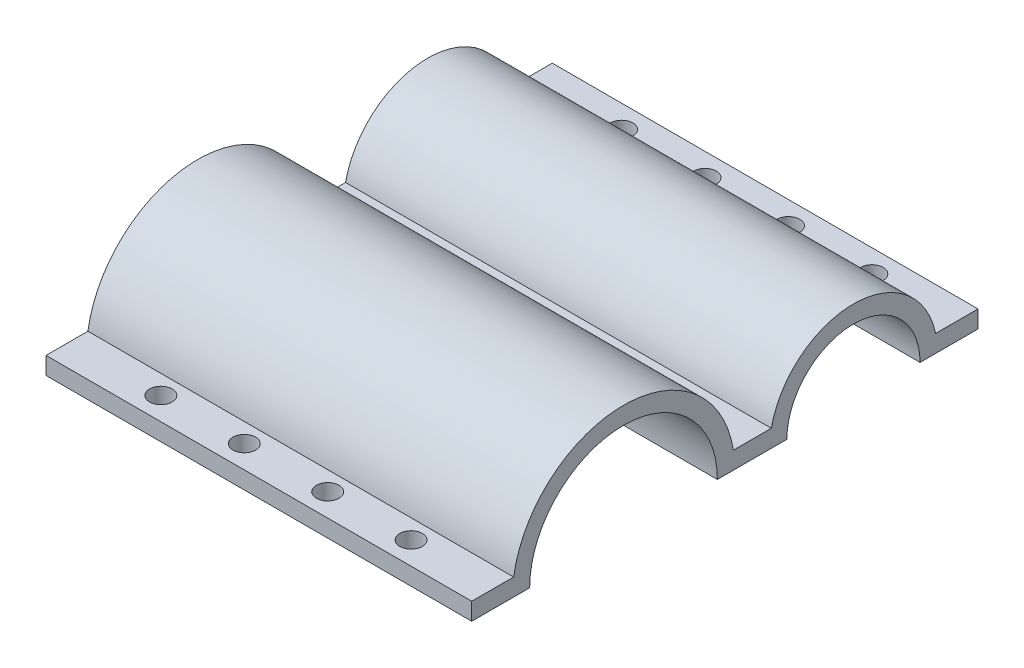
SolidWorks part; units mm, degrees
ref_plane "Front Plane" through (0, 0, 0) normal (0, 0, 1) x (1, 0, 0)
ref_plane "Top Plane" through (0, 0, 0) normal (0, 1, 0) x (1, 0, 0)
ref_plane "Right Plane" through (0, 0, 0) normal (1, 0, 0) x (0, 0, -1)
sketch "Sketch2" plane through (0, 0, 0) normal (1, 0, 0) x (0, 0, -1)
  line L0 (0, 0) -> (-10, 0)
  line L1 (-87.4, 0) -> (-87.4, 3)
  line L3 (0, 3) -> (0, 0)
  line L4 (-33, 0) -> (-45, 0)
  line L5 (-77.4, 0) -> (-87.4, 0)
  line L6 (0, 3) -> (-7.3137, 3)
  line L7 (-35.6863, 3) -> (-42.2358, 3)
  line L8 (-80.1642, 3) -> (-87.4, 3)
  arc A0 (-45, 0) -> (-77.4, 0) centre (-61.2, 0) ccw
  arc A1 (-10, 0) -> (-33, 0) centre (-21.5, 0) ccw
  arc A2 (-7.3137, 3) -> (-35.6863, 3) centre (-21.5, 0) ccw
  arc A3 (-42.2358, 3) -> (-80.1642, 3) centre (-61.2, 0) ccw
  point P9 (-25.1554, 27.7388)
  point P10 (-73.5318, 25.0924)
  point P11 (0, 0)
  point P12 (0, 0)
  dimension "D2" = 16.2
  dimension "D4" = 11.5
  dimension "D3" = 10
  dimension "D1" = 12
  dimension "D6" = 3
extrude "Boss-Extrude1" add sketch "Sketch2" along normal blind 73.5
sketch "Sketch3" plane through (0, 3, 0) normal (0, 1, 0) x (1, 0, 0)
  line L1 (73.5, 0) -> (0, 0) construction
  line L2 (73.5, -3.93) -> (1.5, -3.93) construction
  line L6 (73.5, -87.4) -> (0, -87.4) construction
  line L7 (0, -45) -> (0, -33) construction
  line L8 (0, -39) -> (85.8213, -39) construction
  line L9 (0, -83.47) -> (85.8213, -83.47) construction
  line L10 (0, -45) -> (0, -33) construction
  circle A0 centre (15.9, -3.93) radius 1.95
  circle A1 centre (30.3, -3.93) radius 1.95
  circle A2 centre (44.7, -3.93) radius 1.95
  circle A3 centre (59.1, -3.93) radius 1.95
  circle A4 centre (15.9, -39) radius 1.95
  circle A5 centre (30.3, -39) radius 1.95
  circle A6 centre (44.7, -39) radius 1.95
  circle A7 centre (59.1, -39) radius 1.95
  circle A8 centre (15.9, -83.47) radius 1.95
  circle A9 centre (30.3, -83.47) radius 1.95
  circle A10 centre (44.7, -83.47) radius 1.95
  circle A11 centre (59.1, -83.47) radius 1.95
  point P32 (0, 0)
  point P33 (0, 0)
  point P34 (0, 0)
  point P35 (0, 0)
  point P36 (0, 0)
  point P39 (0, 0)
  point P40 (0, -39)
  point P43 (0, 0)
  point P44 (0, 0)
  point P45 (0, 0)
  point P46 (0, 0)
  point P47 (0, 0)
  point P48 (0, 0)
  point P49 (0, 0)
  point P50 (0, 0)
  point P51 (0, 0)
  point P52 (0, 0)
  point P53 (0, 0)
  point P54 (0.8708, -3.6597)
  dimension "D1" = 3.9
  dimension "D4" = 14.4
  dimension "D5" = 14.4
  dimension "D6" = 14.4
  dimension "D2" = 72
  dimension "D3" = 14.4
  dimension "D7" = 3.93
  dimension "D8" = 3.93
extrude "Cut-Extrude1" cut sketch "Sketch3" against normal up to surface (3 mm away) up to face at (36.75, 0, 82.4)
equation "\"MotorDIA\"= 22'ME 405 Motor Diameter"
equation "\"SyringeDIA\"= 31.4'60ml Syringe Diameter"
equation "\"MotorShaftDIA\"= 6'Motor Shaft Dia"
equation "\"MotorKeyway\"= 1'ME 405 Motor Shaft Keyway Depth"
equation "\"MotorLength\"= 67.5'ME 405 Motor Length Excluding Shaft"
equation "\"SyringeLength\"= 117.3'60ml Syringe Length Excluding Nozzle"
equation "\"3Dtol\"= .5'Sizing Tolerance for 3D printed parts"
equation "\"ChamberDIA\"= 100 - 4'Buoyancy Chamber inner Diameter"
equation "\"ChamberThk\"= 2mm'Buoyancy Chamber Wall Thickness"
equation "\"BearingOD\"= 10"
equation "\"BearingID\"= 4"
equation "\"Bearingwidth\"= 4"
equation "\"ShaftDIA\"= 4"
equation "\"D1@Boss-Extrude1\"=\"MotorLength\"+6"
equation "\"D4@Sketch3\"=\"D3@Sketch3\""
equation "\"D5@Sketch3\"=\"D3@Sketch3\""
equation "\"D6@Sketch3\"=\"D3@Sketch3\""
equation "\"D3@Sketch3\"=\"D2@Sketch3\"/5"
equation "\"D2@Sketch2\"=\"SyringeDIA\"/2+\"3Dtol\""
equation "\"D4@Sketch2\"=\"MotorDIA\"/2+\"3Dtol\""
